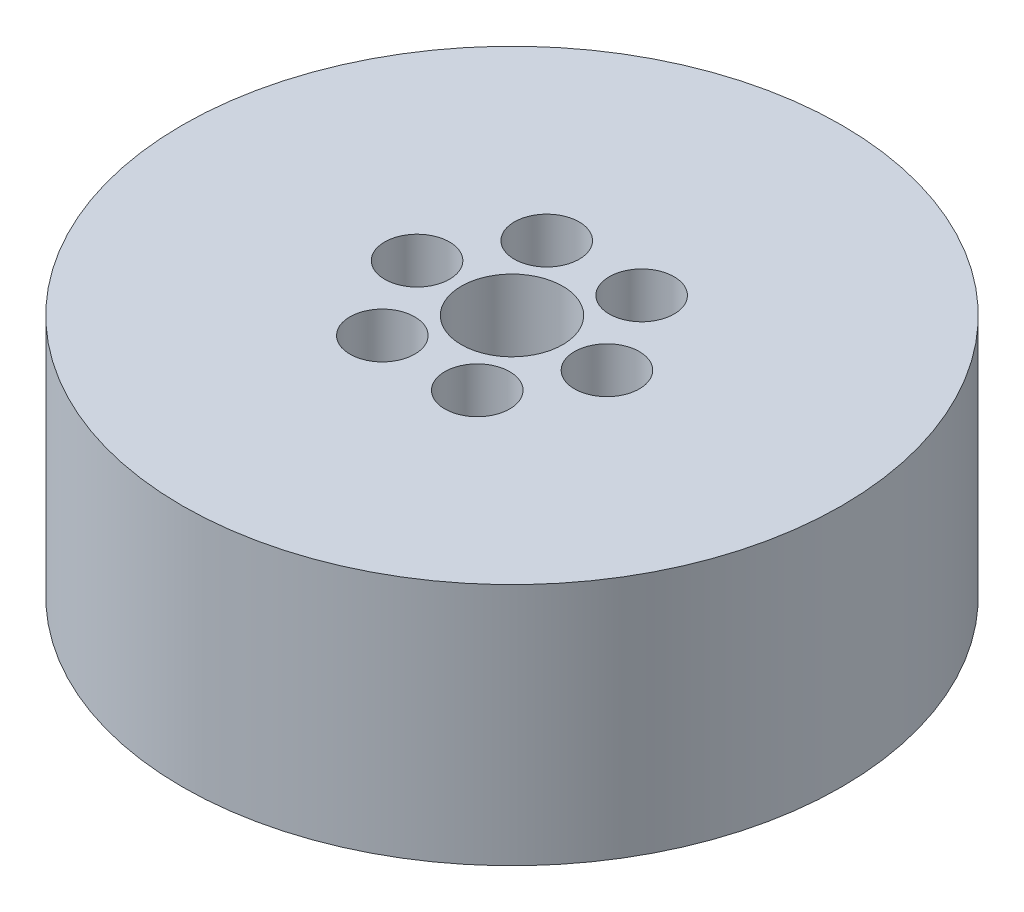
SolidWorks part; units mm, degrees
ref_plane "Front Plane" through (0, 0, 0) normal (0, 0, 1) x (1, 0, 0)
ref_plane "Top Plane" through (0, 0, 0) normal (0, 1, 0) x (1, 0, 0)
ref_plane "Right Plane" through (0, 0, 0) normal (1, 0, 0) x (0, 0, -1)
sketch "Sketch1" plane through (0, 0, 0) normal (0, 1, 0) x (1, 0, 0)
  circle A0 centre (0, 0) radius 32.5
  dimension "FLANGE_OD" = 65
extrude "Boss-Extrude1" add sketch "Sketch1" along normal blind 24
sketch "Sketch2" plane through (0, 0, 0) normal (0, 1, 0) x (1, 0, 0)
  circle A0 centre (0, 0) radius 5
  dimension "BORE_D" = 10
extrude "Cut-Extrude1" cut sketch "Sketch2" along normal through all
sketch "Sketch3" plane through (0, 24, 0) normal (0, 1, 0) x (1, 0, 0)
  circle A0 centre (0, 0) radius 9.357 construction
  circle A1 centre (-9.357, 0) radius 3.194
  dimension "BOLT_D" = 6.3879
  dimension "BOLT_PCD" = 18.7139
extrude "Cut-Extrude2" cut sketch "Sketch3" against normal blind 18.8238
pattern_circular "CirPattern1" count 6 over 360 about axis through (0, 0, 0) along (0, 1, 0) of "Cut-Extrude2"
